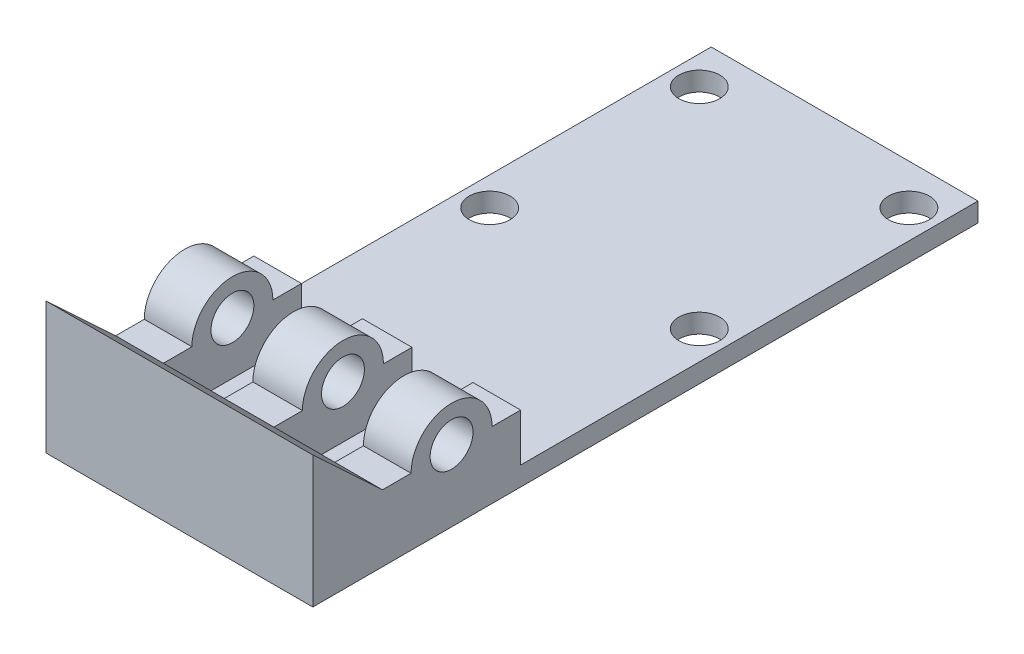
SolidWorks part; units mm, degrees
ref_plane "Front Plane" through (0, 0, 0) normal (0, 0, 1) x (1, 0, 0)
ref_plane "Top Plane" through (0, 0, 0) normal (0, 1, 0) x (1, 0, 0)
ref_plane "Right Plane" through (0, 0, 0) normal (1, 0, 0) x (0, 0, -1)
sketch "Sketch1" plane through (0, 0, 0) normal (1, 0, 0) x (0, 0, -1)
  line L0 (2.25, 1.5) -> (7.25, 1.5)
  line L1 (-2.25, -1.5) -> (2.25, -1.5)
  line L2 (-2.25, -1.5) -> (-2.25, 1.5)
  line L3 (-2.25, 1.5) -> (2.25, 1.5) construction
  line L4 (2.25, -1.5) -> (2.25, 1.5)
  line L5 (-2.25, -1.5) -> (2.25, 1.5) construction
  line L6 (-2.25, 1.5) -> (2.25, -1.5) construction
  line L7 (7.25, 1.5) -> (7.25, 8.5)
  line L8 (7.25, 8.5) -> (4.25, 8.5)
  line L9 (-2.25, 1.5) -> (-7.25, 1.5)
  line L10 (-7.25, 1.5) -> (-7.25, 8.5)
  line L11 (-7.25, 8.5) -> (-4.25, 8.5)
  line L12 (0, 1.5) -> (0, 9) construction
  line L13 (0, 11.25) -> (0, 12.75) construction
  circle A0 centre (0, 9) radius 2.25
  arc A1 (-4.25, 8.5) -> (4.25, 8.5) centre (0, 8.5) cw
  point P0 (0, 0)
  dimension "D10" = 4.5
  dimension "D11" = 1.5
  dimension "D1" = 3
  dimension "D2" = 4.5
  dimension "D3" = 5
  dimension "D4" = 5
  dimension "D5" = 7
  dimension "D6" = 7
  dimension "D7" = 3
  dimension "D8" = 3
  dimension "D9" = 7.5
extrude "Boss-Extrude1" add sketch "Sketch1" along normal mid plane 28
sketch "Sketch2" plane through (0, 0, 7.25) normal (0, 0, 1) x (1, 0, 0)
  line L0 (14, 12.75) -> (-14, 12.75) construction
  line L1 (-9, 12.75) -> (9, 12.75)
  line L2 (-9, 12.75) -> (-9, 3.5)
  line L3 (-9, 3.5) -> (9, 3.5)
  line L4 (9, 12.75) -> (9, 3.5)
  line L5 (-9, 12.75) -> (9, 3.5) construction
  line L6 (-9, 3.5) -> (9, 12.75) construction
  line L7 (-14, 12.75) -> (-14, 8.5) construction
  line L8 (14, 8.5) -> (14, 12.75) construction
  line L9 (14, 1.5) -> (-14, 1.5) construction
  point P4 (0, 8.125)
  dimension "D1" = 5
  dimension "D2" = 5
  dimension "D3" = 2
extrude "Cut-Extrude1" cut sketch "Sketch2" against normal through all
sketch "Sketch4" plane through (0, 0, 0) normal (1, 0, 0) x (0, 0, -1)
  line L5 (-4.25, 8.5) -> (-7.25, 8.5)
  line L6 (-7.25, 8.5) -> (-7.25, 3.5)
  line L7 (-7.25, 3.5) -> (7.25, 3.5)
  line L8 (7.25, 3.5) -> (7.25, 8.5)
  line L9 (7.25, 8.5) -> (4.25, 8.5)
  line L10 (-4.25, 8.5) -> (-7.25, 8.5)
  line L11 (-7.25, 8.5) -> (-7.25, 3.5)
  line L12 (-7.25, 3.5) -> (7.25, 3.5)
  line L13 (7.25, 3.5) -> (7.25, 8.5)
  line L14 (7.25, 8.5) -> (4.25, 8.5)
  circle A0 centre (0, 9) radius 2.25 construction
  arc A1 (4.25, 8.5) -> (-4.25, 8.5) centre (0, 8.5) ccw
  arc A2 (4.25, 8.5) -> (-4.25, 8.5) centre (0, 8.5) ccw
  circle A3 centre (0, 9) radius 2.25
  dimension "D1" = 0
extrude "Boss-Extrude2" add sketch "Sketch4" along normal offset from surface 6.4 and the other way offset from surface 6.4 up to face at (9, 9, -2.25) other way up to face at (-9, 9, 2.25)
sketch "Sketch6" plane through (-14, 0, 0) normal (-1, 0, 0) x (0, 0, 1)
  line L0 (7.25, 8.5) -> (14.5635, 15.32)
  line L1 (7.25, 8.5) -> (7.25, 1.5) construction
  line L2 (7.25, 1.5) -> (14.5635, 8.32)
  line L3 (14.5635, 8.32) -> (14.5635, 15.32)
  line L4 (7.25, 8.5) -> (7.25, 1.5)
  dimension "D1" = 133
  dimension "D2" = 133
  dimension "D3" = 10
extrude "Boss-Extrude3" add sketch "Sketch6" against normal through all
sketch "Sketch7" plane through (-14, 0, 0) normal (-1, 0, 0) x (0, 0, 1)
  line L1 (-2.25, 1.5) -> (2.25, 1.5)
  line L2 (-2.25, 1.5) -> (-2.25, -1.5)
  line L3 (-2.25, -1.5) -> (2.25, -1.5)
  line L4 (2.25, 1.5) -> (2.25, -1.5)
  line L5 (-2.25, 1.5) -> (2.25, -1.5) construction
  line L6 (-2.25, -1.5) -> (2.25, 1.5) construction
  point P4 (0, 0)
extrude "Cut-Extrude2" cut sketch "Sketch7" against normal through all
sketch "Sketch9" plane through (0, 0, -7.25) normal (0, 0, -1) x (-1, 0, 0)
  line L0 (14, 1.5) -> (14, 8.5) construction
  line L1 (-14, 1.5) -> (14, 1.5)
  line L2 (-14, 1.5) -> (-14, 3.5)
  line L3 (-14, 3.5) -> (14, 3.5)
  line L4 (14, 1.5) -> (14, 3.5)
  line L5 (-14, 1.5) -> (14, 3.5) construction
  line L6 (-14, 3.5) -> (14, 1.5) construction
  line L7 (9, 3.5) -> (2.6, 3.5) construction
  point P4 (0, 2.5)
extrude "Boss-Extrude4" add sketch "Sketch9" along normal blind 48
sketch "Sketch11" plane through (0, 3.5, 0) normal (0, 1, 0) x (1, 0, 0)
  line L1 (-14, -14.5635) -> (14, -14.5635)
  line L2 (-14, -14.5635) -> (-14, -7.25)
  line L3 (-14, -7.25) -> (14, -7.25)
  line L4 (14, -14.5635) -> (14, -7.25)
  line L5 (-14, -14.5635) -> (14, -7.25) construction
  line L6 (-14, -7.25) -> (14, -14.5635) construction
  point P4 (0, -10.9068)
extrude "Boss-Extrude5" add sketch "Sketch11" against normal up to surface (2 mm away) and the other way up to surface up to face at (0, 1.5, -24) other way up to face at (0, 4.91, 10.9068)
sketch "Sketch14" plane through (0, 3.5, 0) normal (0, 1, 0) x (1, 0, 0)
  line L0 (11, 55.25) -> (11, 51) construction
  line L1 (-14, 55.25) -> (14, 55.25) construction
  line L2 (11, 51) -> (14, 51) construction
  line L3 (14, 55.25) -> (14, 7.25) construction
  line L4 (0, 55.25) -> (0, 40) construction
  line L5 (0, 40) -> (14, 40) construction
  circle A0 centre (11, 51) radius 2.15
  circle A1 centre (11, 29) radius 2.15
  circle A2 centre (-11, 29) radius 2.15
  circle A3 centre (-11, 51) radius 2.15
  point P21 (0, 40)
  dimension "D3" = 4.3
  dimension "D1" = 3
  dimension "D2" = 4.25
  dimension "D4" = 15.25
  dimension "D5" = 4
extrude "Cut-Extrude6" cut sketch "Sketch14" against normal through all
